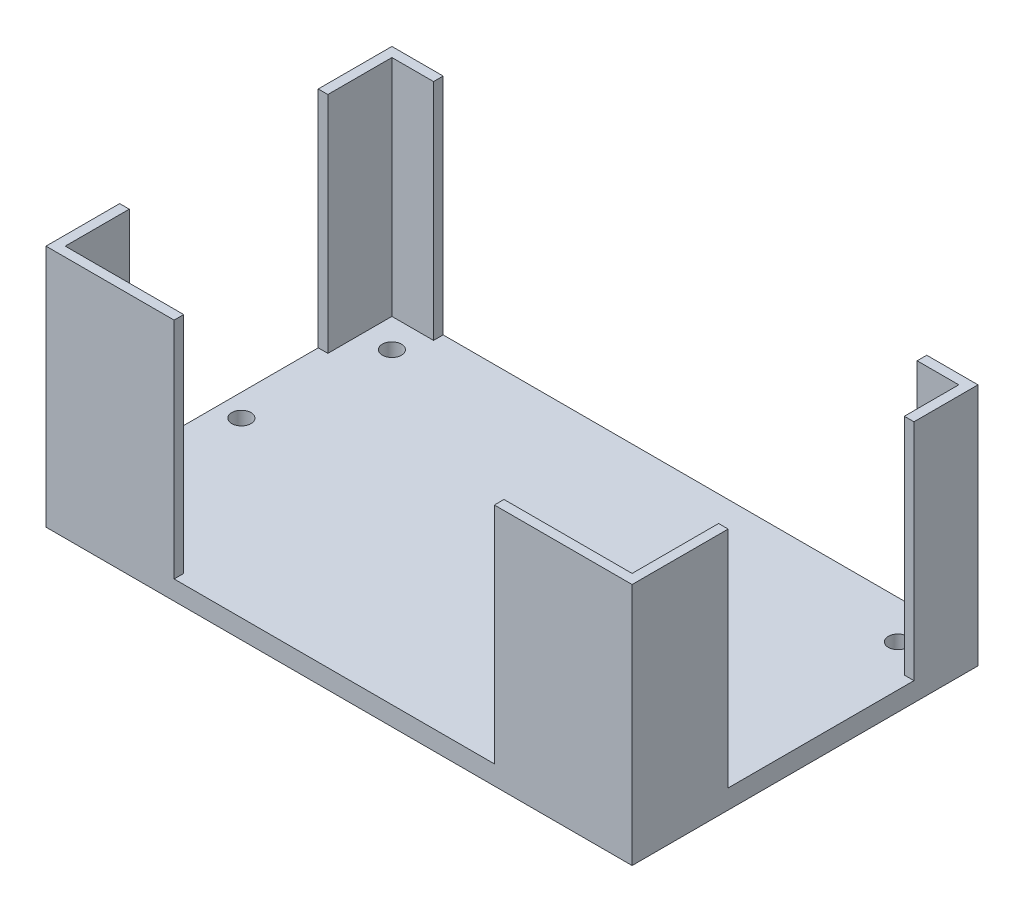
SolidWorks part; units mm, degrees
ref_plane "Front Plane" through (0, 0, 0) normal (0, 0, 1) x (1, 0, 0)
ref_plane "Top Plane" through (0, 0, 0) normal (0, 1, 0) x (1, 0, 0)
ref_plane "Right Plane" through (0, 0, 0) normal (1, 0, 0) x (0, 0, -1)
sketch "Sketch2" plane through (0, 0, 0) normal (0, 1, 0) x (1, 0, 0)
  line L1 (-76.4862, 26.6019) -> (15.0138, 26.6019)
  line L2 (-76.4862, 26.6019) -> (-76.4862, -27.3981)
  line L3 (-76.4862, -27.3981) -> (15.0138, -27.3981)
  line L4 (15.0138, 26.6019) -> (15.0138, -27.3981)
  dimension "D1" = 54
  dimension "D2" = 91.5
extrude "Boss-Extrude1" add sketch "Sketch2" along normal blind 3
sketch "Sketch3" plane through (0, 3, 0) normal (0, 1, 0) x (1, 0, 0)
  line L0 (15.0138, -27.3981) -> (15.0138, 26.6019) construction
  line L1 (15.0138, 26.6019) -> (-76.4862, 26.6019) construction
  circle A0 centre (-14.4862, 11.6019) radius 1.5
  circle A1 centre (-14.4862, -12.3981) radius 1.5
  circle A2 centre (-72.9862, -0.3981) radius 1.5
  dimension "D1" = 3
  dimension "D2" = 3
  dimension "D3" = 3
  dimension "D4" = 29.5
  dimension "D5" = 24
  dimension "D6" = 29.5
  dimension "D7" = 15
  dimension "D8" = 58.5
  dimension "D9" = 27
extrude "Cut-Extrude5" cut sketch "Sketch3" against normal through all
sketch "Sketch5" plane through (0, 0, 0) normal (0, -1, 0) x (-1, 0, 0)
  line L0 (-15.0138, 26.6019) -> (76.4862, 26.6019) construction
  circle A0 centre (27.4862, 14.8519) radius 3.025
  circle A2 centre (27.4862, -15.6481) radius 3.025
  circle A3 centre (57.9862, -15.6481) radius 3.025
  circle A4 centre (57.9862, 14.8519) radius 3.025
  circle A6 centre (14.4862, -12.3981) radius 1.5 construction
  circle A7 centre (14.4862, 11.6019) radius 1.5 construction
  point P10 (0, 0)
  dimension "D1" = 6.05
  dimension "D2" = 6.05
  dimension "D3" = 6.05
  dimension "D4" = 6.05
  dimension "D7" = 13
  dimension "D5" = 30.5
  dimension "D6" = 11.75
  dimension "D8" = 13
  dimension "D9" = 30.5
  dimension "D10" = 30.5
  dimension "D11" = 30.5
  dimension "D12" = 11.75
extrude "Cut-Extrude7" cut sketch "Sketch5" against normal blind 2.5
sketch "Sketch6" plane through (0, 3, 0) normal (0, 1, 0) x (1, 0, 0)
  line L0 (15.0138, -27.3981) -> (15.0138, 26.6019) construction
  line L1 (13.5138, 26.6019) -> (15.0138, 26.6019)
  line L2 (13.5138, 26.6019) -> (13.5138, 16.6019)
  line L3 (13.5138, 16.6019) -> (15.0138, 16.6019)
  line L4 (15.0138, 26.6019) -> (15.0138, 16.6019)
  line L5 (13.5138, -12.3981) -> (15.0138, -12.3981)
  line L6 (13.5138, -12.3981) -> (13.5138, -27.3981)
  line L7 (13.5138, -27.3981) -> (15.0138, -27.3981)
  line L8 (15.0138, -12.3981) -> (15.0138, -27.3981)
  line L9 (15.0138, 26.6019) -> (-76.4862, 26.6019) construction
  line L10 (-76.4862, -27.3981) -> (15.0138, -27.3981) construction
  line L11 (-76.4862, 26.6019) -> (-76.4862, -27.3981) construction
  line L12 (7.0138, 26.6019) -> (15.0138, 26.6019)
  line L13 (7.0138, 26.6019) -> (7.0138, 25.1019)
  line L14 (7.0138, 25.1019) -> (15.0138, 25.1019)
  line L15 (15.0138, 26.6019) -> (15.0138, 25.1019)
  line L16 (-6.4862, -25.8981) -> (13.5138, -25.8981)
  line L17 (-6.4862, -25.8981) -> (-6.4862, -27.3981)
  line L18 (-6.4862, -27.3981) -> (13.5138, -27.3981)
  line L19 (13.5138, -25.8981) -> (13.5138, -27.3981)
  line L20 (-76.4862, -25.8981) -> (-56.4862, -25.8981)
  line L21 (-76.4862, -25.8981) -> (-76.4862, -27.3981)
  line L22 (-76.4862, -27.3981) -> (-56.4862, -27.3981)
  line L23 (-56.4862, -25.8981) -> (-56.4862, -27.3981)
  line L24 (-76.4862, -15.8981) -> (-74.9862, -15.8981)
  line L25 (-76.4862, -15.8981) -> (-76.4862, -25.8981)
  line L26 (-76.4862, -25.8981) -> (-74.9862, -25.8981)
  line L27 (-74.9862, -15.8981) -> (-74.9862, -25.8981)
  line L28 (-76.4862, 25.1019) -> (-74.9862, 25.1019)
  line L29 (-76.4862, 25.1019) -> (-76.4862, 15.1019)
  line L30 (-76.4862, 15.1019) -> (-74.9862, 15.1019)
  line L31 (-74.9862, 25.1019) -> (-74.9862, 15.1019)
  line L32 (-76.4862, 26.6019) -> (-68.4862, 26.6019)
  line L33 (-76.4862, 26.6019) -> (-76.4862, 25.1019)
  line L34 (-76.4862, 25.1019) -> (-68.4862, 25.1019)
  line L35 (-68.4862, 26.6019) -> (-68.4862, 25.1019)
  dimension "D1" = 10
  dimension "D2" = 1.5
  dimension "D3" = 1.5
  dimension "D4" = 15
  dimension "D5" = 0
  dimension "D6" = 0
  dimension "D7" = 0
  dimension "D8" = 0
  dimension "D9" = 1.5
  dimension "D10" = 8
  dimension "D11" = 1.5
  dimension "D12" = 8
  dimension "D13" = 0
  dimension "D14" = 0
  dimension "D15" = 0
  dimension "D16" = 0
  dimension "D17" = 1.5
  dimension "D18" = 1.5
  dimension "D19" = 10
  dimension "D20" = 10
  dimension "D21" = 1.5
  dimension "D22" = 1.5
  dimension "D23" = 20
  dimension "D24" = 20
  dimension "D25" = 0
  dimension "D26" = 0
  dimension "D27" = 0
  dimension "D28" = 0
  dimension "D29" = 0
  dimension "D30" = 0
  dimension "D31" = 0
  dimension "D32" = 0
extrude "Boss-Extrude2" add sketch "Sketch6" along normal blind 35 contours L31 L30 L29 L28 | L32 L35 L34 L33 | L12 L15 L14 L13 | L2 L3 L4 L1 | L6 L7 L8 L5 | L16 L19 L18 L17 | L20 L23 L22 L21 | L25 L26 L27 L24
sketch "Sketch8" plane through (0, 3, 0) normal (0, 1, 0) x (1, 0, 0)
  line L0 (-74.9862, -25.8981) -> (-56.4862, -25.8981) construction
  line L1 (-74.9862, 25.1019) -> (-68.4862, 25.1019) construction
  line L2 (-74.9862, -15.8981) -> (-74.9862, -25.8981) construction
  line L3 (-74.9862, 25.1019) -> (-74.9862, 15.1019) construction
  line L4 (-74.9862, 25.1019) -> (-68.4862, 25.1019) construction
  line L5 (13.5138, 25.1019) -> (13.5138, 16.6019) construction
  line L6 (-6.4862, -25.8981) -> (13.5138, -25.8981) construction
  line L7 (13.5138, -12.3981) -> (13.5138, -25.8981) construction
  circle A0 centre (-70.4862, -21.3981) radius 1.5
  circle A1 centre (-70.4862, 20.6019) radius 1.5
  circle A2 centre (8.5138, -21.3981) radius 1.5
  circle A3 centre (8.5138, 20.6019) radius 1.5
  dimension "D1" = 3
  dimension "D2" = 3
  dimension "D3" = 3
  dimension "D4" = 3
  dimension "D5" = 4.5
  dimension "D6" = 4.5
  dimension "D7" = 4.5
  dimension "D8" = 4.5
  dimension "D9" = 4.5
  dimension "D10" = 5
  dimension "D11" = 4.5
  dimension "D12" = 5
extrude "Cut-Extrude8" cut sketch "Sketch8" against normal through all
sketch "Sketch9" plane through (0, 0, -16.6019) normal (0, 0, 1) x (1, 0, 0)
